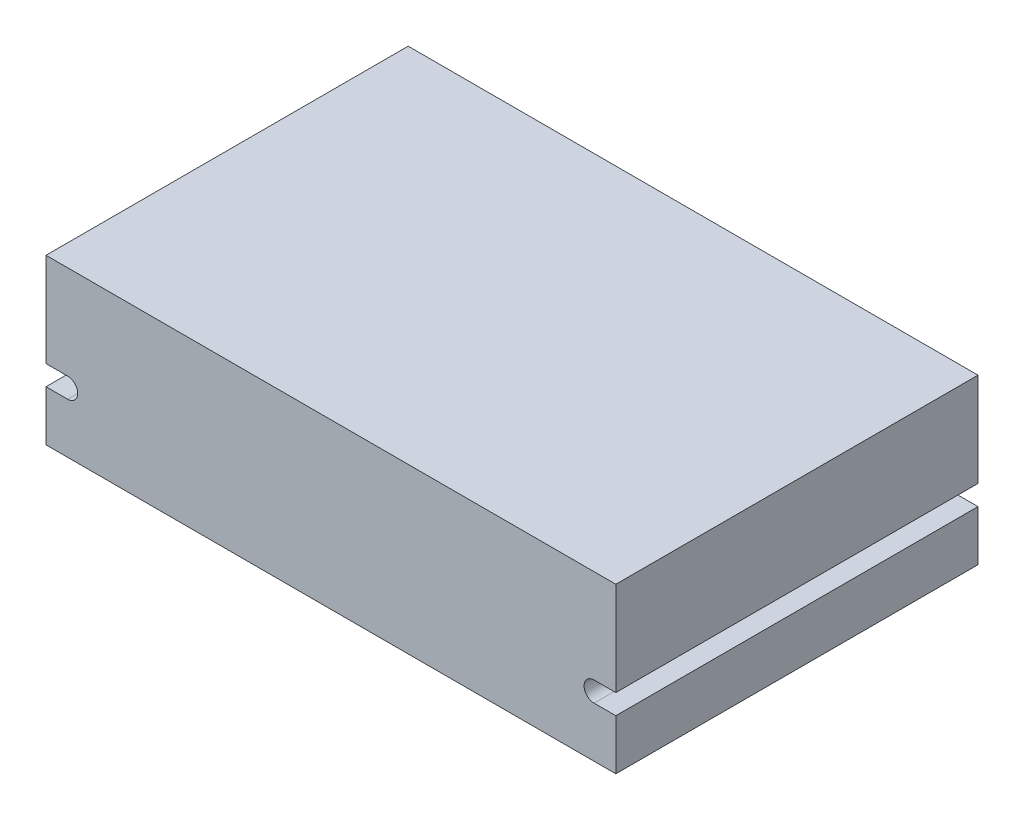
SolidWorks part; units mm, degrees
ref_plane "Piano frontale" through (0, 0, 0) normal (0, 0, 1) x (1, 0, 0)
ref_plane "Piano superiore" through (0, 0, 0) normal (0, 1, 0) x (1, 0, 0)
ref_plane "Piano destro" through (0, 0, 0) normal (1, 0, 0) x (0, 0, -1)
sketch "Schizzo1" plane through (0, 0, 0) normal (0, 0, 1) x (1, 0, 0)
  line L0 (-61.25, -4.5) -> (-52.25, -4.5) construction
  line L1 (-56.75, 17) -> (61.25, 17)
  line L2 (-56.75, 17) -> (-56.75, -2.4268)
  line L3 (-56.75, -17) -> (61.25, -17)
  line L4 (61.25, 17) -> (61.25, -2.4268)
  line L5 (-56.75, -2.4268) -> (-52.25, -2.4268)
  line L6 (-56.75, -6.5732) -> (-52.25, -6.5732)
  line L7 (-56.75, -6.5732) -> (-56.75, -17)
  line L8 (2.25, 17) -> (2.25, -17) construction
  line L9 (61.25, -6.5732) -> (56.75, -6.5732)
  line L10 (61.25, -2.4268) -> (56.75, -2.4268)
  line L11 (61.25, -6.5732) -> (61.25, -17)
  arc A0 (56.75, -6.5732) -> (56.75, -2.4268) centre (56.75, -4.5) cw
  arc A1 (-52.25, -6.5732) -> (-52.25, -2.4268) centre (-52.25, -4.5) ccw
  point P6 (-56.75, -4.5)
  dimension "D1" = 12.5
  dimension "D2" = 4.5
extrude "Estrusione-Estrusione1" add sketch "Schizzo1" along normal blind 75
